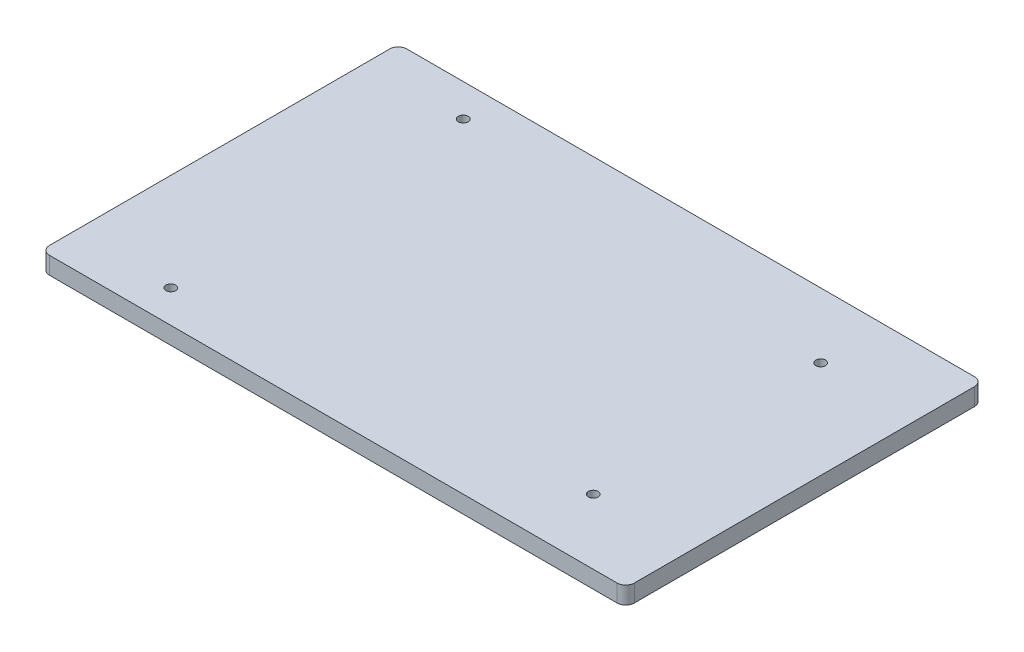
SolidWorks part; units mm, degrees
ref_plane "Alzado" through (0, 0, 0) normal (0, 0, 1) x (1, 0, 0)
ref_plane "Planta" through (0, 0, 0) normal (0, 1, 0) x (1, 0, 0)
ref_plane "Vista lateral" through (0, 0, 0) normal (1, 0, 0) x (0, 0, -1)
sketch "Croquis1" plane through (0, 0, 0) normal (0, 1, 0) x (1, 0, 0)
  line L1 (135, -82.5) -> (-135, -82.5)
  line L2 (135, -82.5) -> (135, 82.5)
  line L3 (135, 82.5) -> (-135, 82.5)
  line L4 (-135, -82.5) -> (-135, 82.5)
  line L5 (135, -82.5) -> (-135, 82.5) construction
  line L6 (135, 82.5) -> (-135, -82.5) construction
  point P0 (0, 0)
  dimension "D1" = 165
  dimension "D2" = 270
extrude "Saliente-Extruir1" add sketch "Croquis1" along normal blind 8
fillet "Redondeo1" radius 4 4 edges at (-135, 4, -82.5) (135, 4, -82.5) (135, 4, 82.5) (-135, 4, 82.5)
sketch "Croquis2" plane through (0, 8, 0) normal (0, 1, 0) x (1, 0, 0)
  line L0 (131, 82.5) -> (-131, 82.5) construction
  line L1 (135, -78.5) -> (135, 78.5) construction
  circle A0 centre (90, 52.5) radius 2.25
  dimension "D1" = 4.5
  dimension "D2" = 30
  dimension "D3" = 45
extrude "Cortar-Extruir1" cut sketch "Croquis2" against normal through all
mirror "Simetría1" about plane through (0, 0, 0) normal (0, 0, 1) of "Cortar-Extruir1"
sketch "Croquis3" plane through (0, 8, 0) normal (0, 1, 0) x (1, 0, 0)
  line L0 (-135, 78.5) -> (-135, -78.5) construction
  line L1 (131, 82.5) -> (-131, 82.5) construction
  line L2 (-135, 0) -> (-113.8944, 0) construction
  circle A0 centre (-90, 67.5) radius 2.25
  circle A1 centre (-90, -67.5) radius 2.25
  dimension "D1" = 4.5
  dimension "D2" = 45
  dimension "D3" = 15
extrude "Cortar-Extruir2" cut sketch "Croquis3" against normal through all
